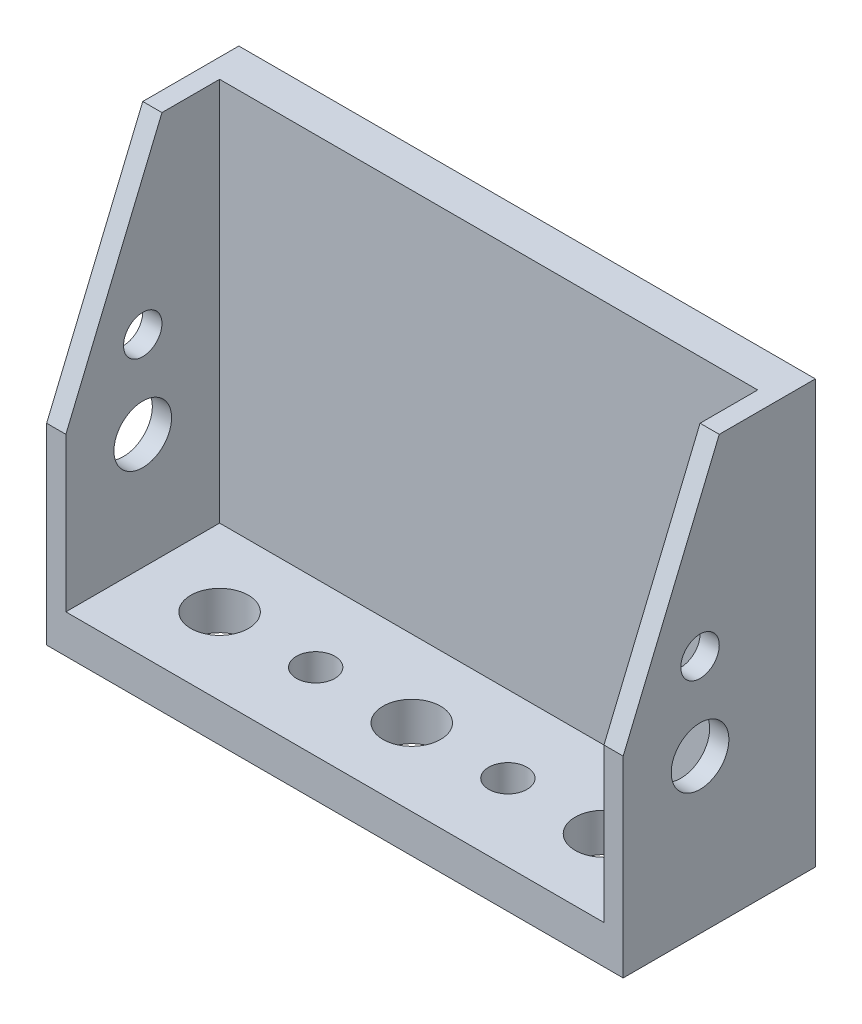
SolidWorks part; units mm, degrees
ref_plane "Front Plane" through (0, 0, 0) normal (0, 0, 1) x (1, 0, 0)
ref_plane "Top Plane" through (0, 0, 0) normal (0, 1, 0) x (1, 0, 0)
ref_plane "Right Plane" through (0, 0, 0) normal (1, 0, 0) x (0, 0, -1)
sketch "Sketch1" plane through (0, 0, 0) normal (0, 1, 0) x (1, 0, 0)
  line L1 (-15, -5) -> (15, -5)
  line L2 (-15, -5) -> (-15, 5)
  line L3 (-15, 5) -> (15, 5)
  line L4 (15, -5) -> (15, 5)
  line L5 (-15, -5) -> (15, 5) construction
  line L6 (-15, 5) -> (15, -5) construction
  point P0 (0, 0)
  dimension "D1" = 30
  dimension "D2" = 10
extrude "Boss-Extrude1" add sketch "Sketch1" along normal blind 2
sketch "Sketch2" plane through (0, 2, 0) normal (0, 1, 0) x (1, 0, 0)
  line L0 (15, -5) -> (15, 5) construction
  line L1 (-15, 5) -> (15, 5)
  line L2 (-15, 5) -> (-15, 3)
  line L3 (-15, 3) -> (15, 3)
  line L4 (15, 5) -> (15, 3)
  dimension "D1" = 2
extrude "Boss-Extrude2" add sketch "Sketch2" along normal blind 20
sketch "Sketch3" plane through (15, 0, 0) normal (1, 0, 0) x (0, 0, -1)
  line L0 (-5, 2) -> (-5, 10)
  line L1 (-5, 10) -> (0, 22)
  line L2 (0, 22) -> (3, 22)
  line L3 (3, 22) -> (3, 2)
  line L4 (3, 2) -> (-5, 2)
  dimension "D1" = 8
  dimension "D2" = 3
extrude "Boss-Extrude3" add sketch "Sketch3" against normal blind 1
extrude "Boss-Extrude4" add sketch "Sketch3<2>" along normal blind 1 from surface starting at face at (-15, 8, -1)
sketch "Sketch3<2>" plane through (15, 0, 0) normal (1, 0, 0) x (0, 0, -1) same geometry as "Sketch3"
sketch "Sketch4" plane through (0, 0, 0) normal (0, -1, 0) x (1, 0, 0)
  line L0 (0, -5.5) -> (0, 5.5) construction
  line L1 (-15, 5) -> (15, 5) construction
  circle A0 centre (0, 1) radius 1.5
  circle A1 centre (5, 1) radius 1
  circle A2 centre (-5, 1) radius 1
  circle A3 centre (10, 1) radius 1.5
  circle A4 centre (-10, 1) radius 1.5
  point P14 (0, 0)
  dimension "D2" = 3
  dimension "D5" = 2
  dimension "D6" = 2
  dimension "D7" = 3
  dimension "D8" = 3
  dimension "D1" = 4
  dimension "D3" = 5
  dimension "D4" = 5
  dimension "D9" = 5
  dimension "D10" = 5
extrude "Cut-Extrude1" cut sketch "Sketch4" against normal blind 11
sketch "Sketch5" plane through (15, 0, 0) normal (1, 0, 0) x (0, 0, -1)
  line L0 (-5, 10) -> (-5, 0) construction
  line L1 (5.5, 0) -> (-5.5, 0) construction
  circle A0 centre (-1, 8) radius 1.5
  circle A1 centre (-1, 12.5) radius 1
  point P6 (0, 0)
  dimension "D4" = 2
  dimension "D5" = 3
  dimension "D1" = 4
  dimension "D2" = 8
  dimension "D3" = 4.5
extrude "Cut-Extrude2" cut sketch "Sketch5" against normal blind 41
